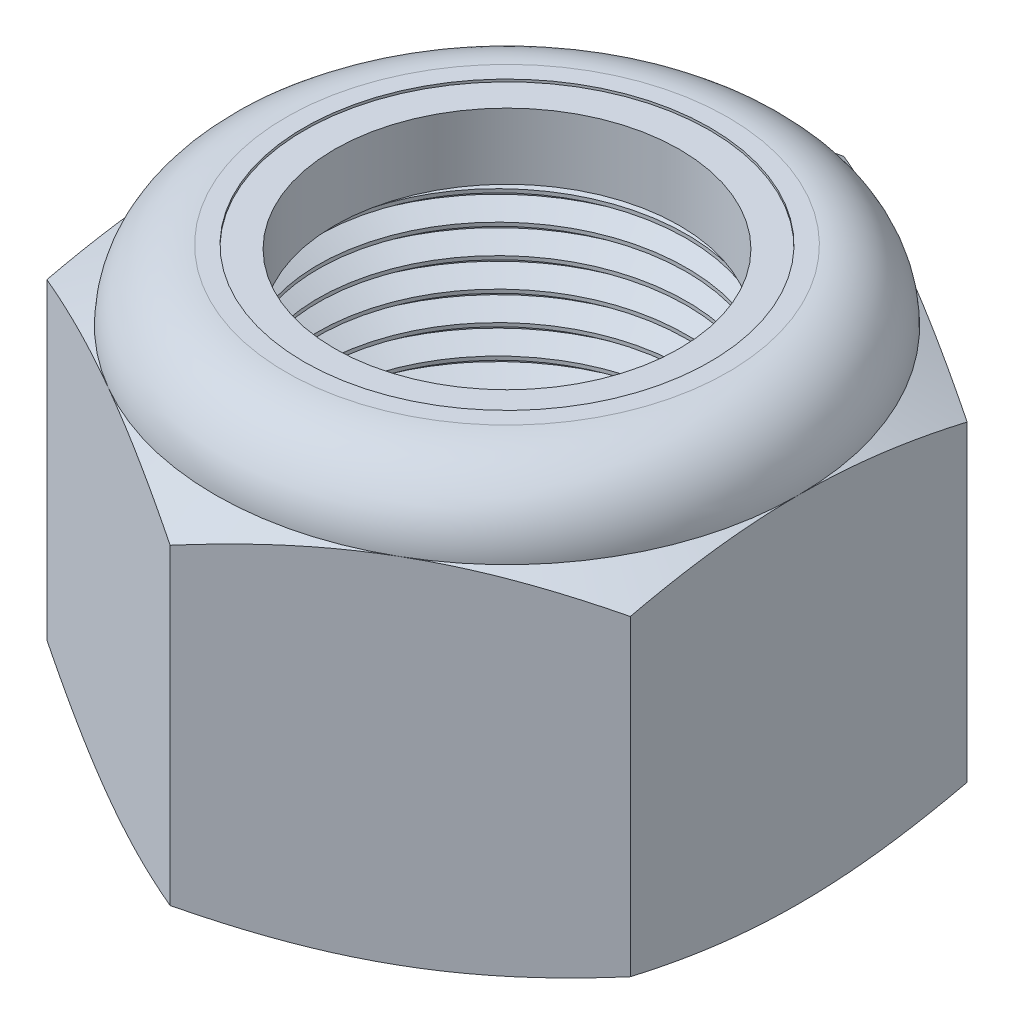
SolidWorks part; units mm, degrees
note: '?' marks a value the reader was unsure of.
ref_plane "Front" through (0, 0, 0) normal (0, 0, 1) x (1, 0, 0)
ref_plane "Top" through (0, 0, 0) normal (0, 1, 0) x (1, 0, 0)
ref_plane "Right" through (0, 0, 0) normal (1, 0, 0) x (0, 0, -1)
sketch "Sketch8" plane through (0, 0, 0) normal (1, 0, 0) x (0, 0, -1)
  line L0 (0, 0) -> (0, 26.5906) construction
  line L1 (18.2562, 0) -> (-18.2562, 0) construction
  line L2 (-12.7, 26.5906) -> (12.7, 26.5906) construction
  line L3 (12.7, 26.5906) -> (12.7, 24.7763) construction
sketch "Sketch1" plane through (0, 0, 0) normal (0, 1, 0) x (1, 0, 0)
  line L1 (0, 21.0805) -> (-18.2562, 10.5403)
  line L2 (-18.2562, 10.5403) -> (-18.2562, -10.5403)
  line L3 (-18.2562, -10.5403) -> (0, -21.0805)
  line L4 (0, -21.0805) -> (18.2563, -10.5403)
  line L5 (18.2563, -10.5403) -> (18.2563, 10.5403)
  line L6 (18.2563, 10.5403) -> (0, 21.0805)
  circle A0 centre (0, 0) radius 18.2562 construction
  circle A1 centre (0, 0) radius 12.7
extrude "Extrude1" add sketch "Sketch1" along normal up to vertex (26.5906 mm away) up to point (0, 26.5906, 0)
sketch "Sketch5" plane through (0, 0, 0) normal (1, 0, 0) x (0, 0, -1)
  line L0 (0, 0) -> (18.2562, 0)
  line L1 (18.2562, 0) -> (21.0805, 1.317)
  line L2 (21.0805, 1.317) -> (21.0805, 20.8419)
  line L3 (21.0805, 20.8419) -> (18.2562, 22.1589)
  line L4 (13.8245, 26.5906) -> (13.8245, 27.8606)
  line L5 (13.8245, 27.8606) -> (22.3505, 27.8606)
  line L6 (22.3505, 27.8606) -> (22.3505, -1.27)
  line L7 (22.3505, -1.27) -> (0, -1.27)
  line L8 (0, -1.27) -> (0, 0)
  line L9 (18.2562, 22.1589) -> (18.2562, 0) construction
  line L12 (21.0805, 26.5906) -> (21.0805, 0) construction
  line L13 (21.0805, 13.2953) -> (22.3505, 13.2953) construction
  line L15 (0, 0) -> (0, 27.8606) construction
  line L18 (18.2562, 0) -> (-18.2562, 0) construction
  line L19 (10.5403, 26.5906) -> (21.0805, 26.5906) construction
  line L20 (0, 27.8606) -> (13.8245, 27.8606) construction
  line L21 (10.5403, 0) -> (21.0805, 0) construction
  arc A0 (18.2562, 22.1589) -> (13.8245, 26.5906) centre (13.8245, 22.1589) ccw
  dimension "D1" = 25
  dimension "D2" = 1.27
  dimension "D4" = 4.4318
revolve "Cut-Revolve3" cut sketch "Sketch5" angle 360 about L15
sketch "Sketch4" plane through (0, 0, 0) normal (1, 0, 0) x (0, 0, -1)
  line L0 (0, 22.1589) -> (13.97, 22.1589)
  line L1 (13.97, 22.1589) -> (0, 15.6445)
  line L3 (0, 6.5143) -> (13.97, 0)
  line L4 (13.97, 0) -> (0, 0)
  line L5 (0, 0) -> (0, 22.1589) construction
  line L10 (0, 0) -> (0, 26.5906) construction
  line L11 (0, 6.5143) -> (0, 0)
  line L12 (0, 22.1589) -> (0, 15.6445)
  line L13 (15.8104, 22.1589) -> (0, 22.1589) construction
  dimension "D1" = 25
  dimension "D2" = 27.94
sketch "Sketch6" plane through (0, 0, 0) normal (1, 0, 0) x (0, 0, -1)
  line L0 (0, 22.1589) -> (18.1038, 22.1589)
  line L1 (13.8245, 26.4382) -> (6.9122, 26.4382)
  line L2 (0, 27.8606) -> (0, 22.1589)
  line L3 (6.9122, 27.8606) -> (0, 27.8606)
  line L4 (0, 27.8606) -> (13.8245, 27.8606) construction
  line L5 (0, 0) -> (0, 27.8606) construction
  line L6 (0, 27.8606) -> (0, 0) construction
  line L7 (6.9122, 26.4382) -> (6.9122, 27.8606)
  line L8 (13.8245, 26.5906) -> (13.8245, 26.4382) construction
  line L9 (6.9122, 26.4382) -> (0, 26.4382) construction
  line L10 (0, 26.4382) -> (0, 15.6445) construction
  arc A0 (18.1038, 22.1589) -> (13.8245, 26.4382) centre (13.8245, 22.1589) ccw
  arc A1 (18.2562, 22.1589) -> (13.8245, 26.5906) centre (13.8245, 22.1589) ccw construction
  dimension "D1" = 0.1524
revolve "Cut-Revolve4" cut sketch "Sketch6" angle 360 about L6
revolve "Cut-Revolve2" cut sketch "Sketch4" angle 360 about L5
sketch "Sketch7" plane through (0, 0, 0) normal (1, 0, 0) x (0, 0, -1)
  line L0 (10.795, 22.2351) -> (18.027, 22.2351)
  line L1 (13.8245, 26.362) -> (10.795, 26.362)
  line L2 (10.795, 26.362) -> (10.795, 22.2351)
  line L3 (10.795, 22.2351) -> (0, 22.2351) construction
  line L4 (0, 22.2351) -> (0, 26.362) construction
  line L5 (0, 26.362) -> (10.795, 26.362) construction
  line L6 (10.795, 22.2351) -> (10.795, 22.1589) construction
  line L7 (0, 22.1589) -> (18.1038, 22.1589) construction
  line L8 (13.8245, 26.362) -> (13.8245, 26.4382) construction
  arc A0 (18.027, 22.2351) -> (13.8245, 26.362) centre (13.8245, 22.1589) ccw
  arc A2 (18.1038, 22.1589) -> (13.8245, 26.4382) centre (13.8245, 22.1589) ccw construction
  dimension "D1" = 0.0762
  dimension "D2" = 21.59
revolve "Revolve2" add sketch "Sketch7" angle 360 about L4
sketch "Sketch2" plane through (0, 0, 0) normal (1, 0, 0) x (0, 0, -1)
  line L0 (-12.7, 0) -> (-12.7, 22.1589) construction
  line L1 (0, 0) -> (12.7, 0)
  line L2 (0, 0) -> (0, 22.1589)
  line L3 (0, 22.1589) -> (12.7, 22.1589)
  line L4 (12.7, 0) -> (12.7, 22.1589)
  line L6 (15.8104, 22.1589) -> (18.2562, 22.1589) construction
  line L7 (0, -12.7) -> (0, 0) construction
revolve "Revolve1" add sketch "Sketch2" angle 360 about L7
sketch "Sketch9" plane through (0, 0, 0) normal (1, 0, 0) x (0, 0, -1)
  line L0 (12.8964, 23.8597) -> (12.8964, 22.0455) construction
  line L1 (12.8964, 22.0455) -> (11.3252, 22.9526) construction
  line L2 (11.3252, 22.9526) -> (12.8964, 23.8597) construction
  line L3 (11.5216, 23.066) -> (11.5216, 22.8392) construction
  line L4 (12.7, 23.7464) -> (12.7, 22.1589) construction
  line L5 (11.3252, 22.9526) -> (11.5216, 22.9526) construction
  line L6 (12.7, 22.9526) -> (12.8964, 22.9526) construction
  line L7 (12.7982, 22.9526) -> (12.7982, 23.8031) construction
  line L8 (12.8964, 22.0455) -> (12.7982, 23.8031)
  line L9 (12.7982, 23.8031) -> (11.5216, 23.066)
  line L10 (11.5216, 23.066) -> (11.5216, 22.8392)
  line L11 (11.5216, 22.8392) -> (12.8964, 22.0455)
  dimension "D1" = 1.8143
  dimension "D2" = 0.2268
sketch "Sketch10" plane through (0, 22.1589, 0) normal (0, 1, 0) x (1, 0, 0)
  circle A1 centre (0, 0) radius 12.7
  circle A2 centre (0, 0) radius 12.7
  dimension "D1" = 0
curve "Helix/Spiral1" pitch 1.8143 height 28.4049 turns 15.6563
sweep "Cut-Sweep1" cut profiles "Sketch9" path "Helix/Spiral1" align with end faces yes
sketch "Sketch11" plane through (0, 0, 0) normal (1, 0, 0) x (0, 0, -1)
  line L0 (0, 0) -> (0, 26.5906) construction
  line L1 (18.2562, 0) -> (-18.2562, 0) construction
  line L4 (0, 26.5906) -> (0, 0) construction
  line L5 (0, 13.2953) -> (12.7, 13.2953) construction
  line L6 (0, 0) -> (13.97, 0)
  line L7 (0, 6.5143) -> (0, 0)
  line L8 (13.97, 0) -> (0, 6.5143)
  dimension "D1" = 27.94
  dimension "D2" = 25
revolve "Revolve3" add sketch "Sketch11" angle 360 about L4
sketch "Sketch12" plane through (0, 0, 0) normal (1, 0, 0) x (0, 0, -1)
  line L0 (13.97, 22.1589) -> (0, 22.1589)
  line L1 (0, 22.1589) -> (0, 0)
  line L2 (0, 0) -> (13.97, 0)
  line L3 (18.2562, 0) -> (-18.2562, 0) construction
  line L4 (13.97, 0) -> (13.97, 22.1589)
  line L5 (-13.97, 0) -> (13.97, 0) construction
revolve "Revolve4" add sketch "Sketch12" angle 360 about L0
combine bodies "Combine1" operation type subtract main body 136 bodies to subtract 133
ref_plane "Contact Plane 1" through (0, 0, 0) normal (0, -1, 0) x (1, 0, 0)
ref_axis "Center Axis 1" through (0, -2.1015, 0) along (0, 1, 0)?
equation "\"D4@Sketch5\"=\"Height@Sketch8\"/6"
equation "\"D1@Sketch9\"=\"Thread Pitch@Sketch8\""
equation "\"D2@Sketch9\"=\"Thread Pitch@Sketch8\"/8"
equation "\"D4@Helix/Spiral1\"=\"Thread Pitch@Sketch8\""
equation "\"D3@Helix/Spiral1\"=\"Thread Pitch@Sketch8\"+\"Height@Sketch8\""
equation "\"D2@Sketch4\"=\"Thread Dia@Sketch8\"*1.1"
equation "\"D1@Sketch11\"=\"Thread Dia@Sketch8\"*1.1"
equation "\"D2@Sketch7\"=\"Thread Dia@Sketch8\"*.85"
